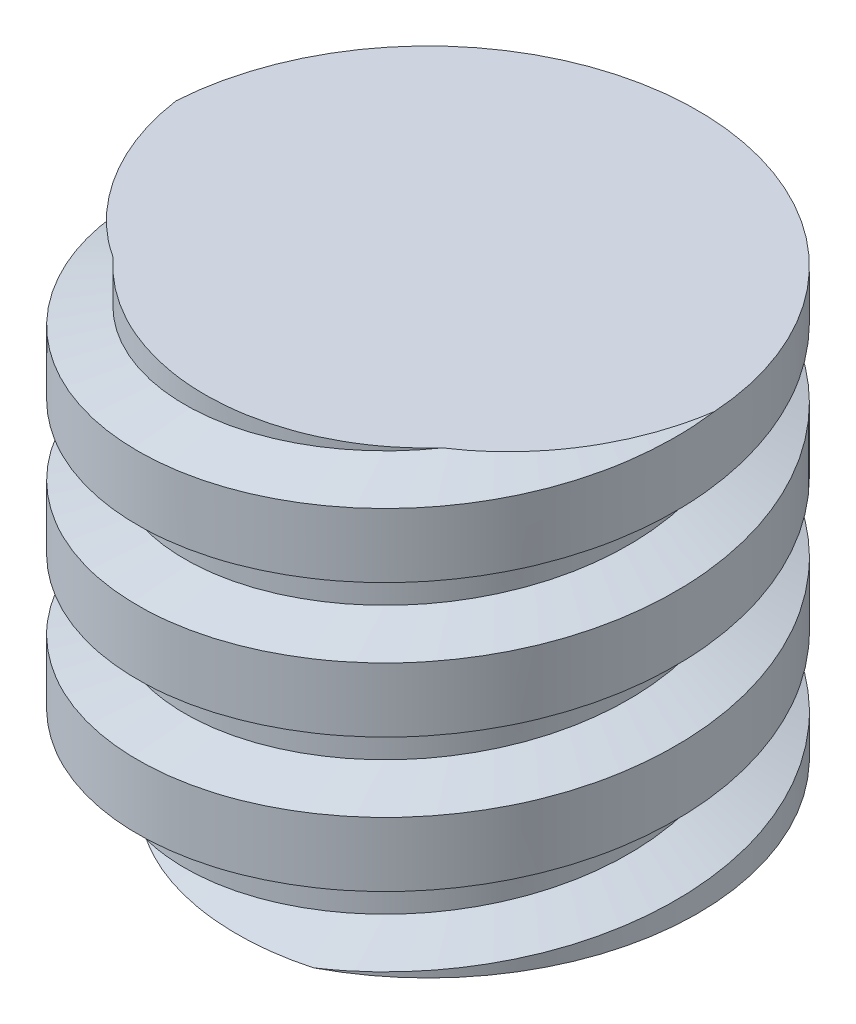
SolidWorks part; units mm, degrees
ref_plane "Спереди" through (0, 0, 0) normal (0, 0, 1) x (1, 0, 0)
ref_plane "Сверху" through (0, 0, 0) normal (0, 1, 0) x (1, 0, 0)
ref_plane "Справа" through (0, 0, 0) normal (1, 0, 0) x (0, 0, -1)
sketch "Эскиз3" plane through (0, 0, 0) normal (0, 0, 1) x (1, 0, 0)
  line L0 (0, 0) -> (0, 16.0133) construction
  line L1 (0, 0) -> (9.5, 0)
  line L2 (9.5, 0) -> (9.5, 15)
  line L3 (9.5, 15) -> (0, 15)
  line L4 (0, 15) -> (0, 0)
  line L5 (0, 16.0133) -> (15.8419, 16.0133) construction
  line L6 (0, 0) -> (0, 40.7619) construction
  dimension "D1" = 9.5
  dimension "D2" = 15
revolve "Повернуть1" add sketch "Эскиз3" angle 360 about L0
sketch "Эскиз6" plane through (0, 15, 0) normal (0, 1, 0) x (1, 0, 0)
  circle A1 centre (0, 0) radius 9.5
  circle A2 centre (0, 0) radius 9.5
  dimension "D1" = 0
curve "Спираль1" pitch 4.712 height 36.518 turns 7.75
sketch "Эскиз7" plane through (0, 0, 0) normal (1, 0, 0) x (0, 0, -1)
  line L0 (-9.5, 12.8871) -> (-9.5, -1.6217) construction
  line L1 (-9.5, 15) -> (-9.5, 0) construction
  line L2 (-9.5, 16.225) -> (-9.5, 13.775) construction
  line L4 (-7.85, 14.3756) -> (-7.85, 15.6244)
  line L5 (-7.85, 15.6244) -> (-11.15, 16.8256)
  line L6 (-11.15, 16.8256) -> (-11.15, 13.1744)
  line L7 (-11.15, 13.1744) -> (-7.85, 14.3756)
  line L9 (-11.15, 15) -> (-1.3827, 15) construction
  point P13 (-9.5, 15)
  dimension "D1" = 3.3
  dimension "D2" = 20
  dimension "D3" = 2.45
sweep "Вырез-По траектории1" cut profiles "Эскиз7" path "Спираль1" align with end faces yes
